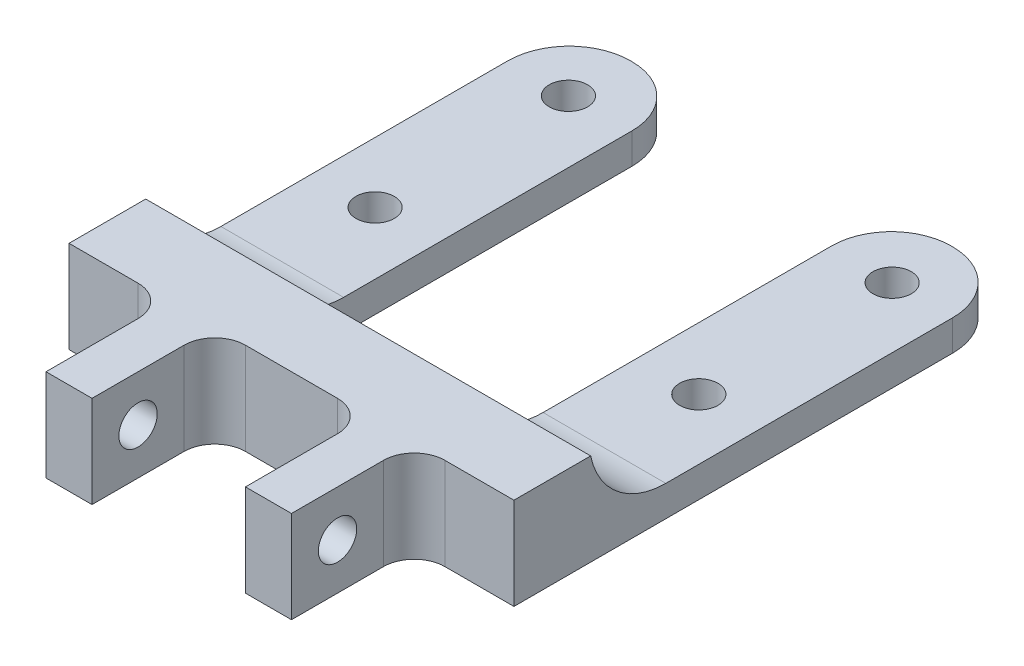
SolidWorks part; units mm, degrees
ref_plane "Front Plane" through (0, 0, 0) normal (0, 0, 1) x (1, 0, 0)
ref_plane "Top Plane" through (0, 0, 0) normal (0, 1, 0) x (1, 0, 0)
ref_plane "Right Plane" through (0, 0, 0) normal (1, 0, 0) x (0, 0, -1)
sketch "Sketch1" plane through (0, 0, 0) normal (0, 1, 0) x (1, 0, 0)
  line L0 (24.9, 27.6) -> (25, 27.6)
  line L1 (0, 0) -> (29, 0)
  line L2 (0, 0) -> (0, 23.6)
  line L3 (4, 27.6) -> (4.1, 27.6)
  line L4 (29, 0) -> (29, 23.6)
  line L6 (8, 23.7) -> (8, 3.5)
  line L7 (8, 3.5) -> (21, 3.5)
  line L8 (21, 23.7) -> (21, 3.5)
  circle A0 centre (3.95, 23.6) radius 1.25
  circle A1 centre (25.05, 23.6) radius 1.25
  circle A2 centre (25.05, 11) radius 1.25
  circle A3 centre (3.95, 11) radius 1.25
  arc A4 (0, 23.6) -> (4, 27.6) centre (4, 23.6) cw
  arc A5 (25, 27.6) -> (29, 23.6) centre (25, 23.6) cw
  arc A6 (24.9, 27.6) -> (21, 23.7) centre (24.9, 23.7) ccw
  arc A7 (4.1, 27.6) -> (8, 23.7) centre (4.1, 23.7) cw
  point P19 (0, 27.6)
  point P22 (29, 27.6)
  dimension "D7" = 2.5
  dimension "D8" = 2.5
  dimension "D9" = 2.5
  dimension "D10" = 2.5
  dimension "D18" = 4
  dimension "D19" = 3.9
  dimension "D1" = 29
  dimension "D2" = 27.6
  dimension "D3" = 21.1
  dimension "D4" = 3.95
  dimension "D5" = 21.1
  dimension "D6" = 3.95
  dimension "D11" = 11
  dimension "D12" = 11
  dimension "D13" = 12.6
  dimension "D14" = 12.6
  dimension "D15" = 8
  dimension "D16" = 8
  dimension "D17" = 3.5
extrude "Boss-Extrude1" add sketch "Sketch1" along normal blind 2 contours L3 L8 L7 L6 L2 L1 L4 A3 A2 A1 A0 region at (24.95, 0, -27.1997)
sketch "Sketch2" plane through (0, 2, 0) normal (0, 1, 0) x (1, 0, 0)
  line L1 (0, 0) -> (29, 0)
  line L2 (0, 0) -> (0, -5)
  line L3 (0, -5) -> (29, -5)
  line L4 (29, 0) -> (29, -5)
  dimension "D1" = 5
extrude "Boss-Extrude2" add sketch "Sketch2" along normal blind 4 and the other way blind 2
fillet "Fillet1" radius 5 1 edges at (14.5, 2, 0)
sketch "Sketch3" plane through (0, 0, 5) normal (0, 0, 1) x (1, 0, 0)
  line L0 (0, 6) -> (29, 6) construction
  line L1 (9.5, 6) -> (6.5, 6)
  line L2 (9.5, 6) -> (9.5, 0)
  line L3 (9.5, 0) -> (6.5, 0)
  line L4 (6.5, 6) -> (6.5, 0)
  line L5 (0, 0) -> (29, 0) construction
  line L7 (0, 0) -> (0, 6) construction
  line L8 (29, 0) -> (29, 6) construction
  line L9 (19.5, 0) -> (22.5, 0)
  line L10 (19.5, 0) -> (19.5, 6)
  line L11 (19.5, 6) -> (22.5, 6)
  line L12 (22.5, 0) -> (22.5, 6)
  dimension "D1" = 3
  dimension "D2" = 6.5
  dimension "D3" = 6.5
  dimension "D4" = 3
extrude "Boss-Extrude3" add sketch "Sketch3" along normal blind 8
fillet "Fillet2" radius 2 4 edges at (9.5, 3, 5) (6.5, 3, 5) (19.5, 3, 5) (22.5, 3, 5)
sketch "Sketch4" plane through (9.5, 0, 0) normal (1, 0, 0) x (0, 0, -1)
  line L0 (-13, 6) -> (-7, 6) construction
  line L1 (-7, 0) -> (-7, 6) construction
  circle A0 centre (-10, 3) radius 1.25
  dimension "D3" = 2.5
  dimension "D1" = 3
  dimension "D2" = 3
extrude "Cut-Extrude1" cut sketch "Sketch4" against normal blind 7 and the other way blind 15
